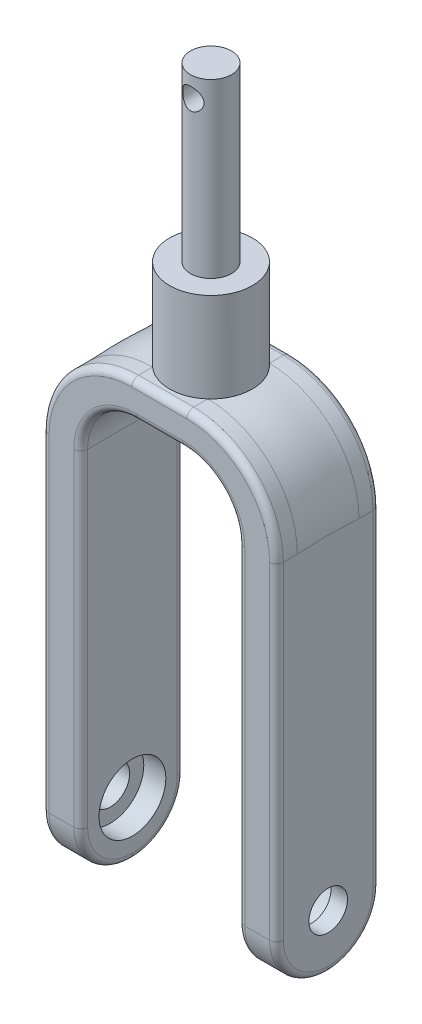
SolidWorks part; units mm, degrees
ref_plane "前视基准面" through (0, 0, 0) normal (0, 0, 1) x (1, 0, 0)
ref_plane "上视基准面" through (0, 0, 0) normal (0, 1, 0) x (1, 0, 0)
ref_plane "右视基准面" through (0, 0, 0) normal (1, 0, 0) x (0, 0, -1)
sketch "草图1" plane through (0, 0, 0) normal (0, 1, 0) x (1, 0, 0)
  line L1 (17, 7.5) -> (-17, 7.5)
  line L2 (17, 7.5) -> (17, -7.5)
  line L3 (17, -7.5) -> (-17, -7.5)
  line L4 (-17, 7.5) -> (-17, -7.5)
  line L5 (17, 7.5) -> (-17, -7.5) construction
  line L6 (17, -7.5) -> (-17, 7.5) construction
  point P0 (0, 0)
extrude "凸台-拉伸1" add sketch "草图1" against normal blind 68
sketch "草图2" plane through (0, 0, 0) normal (0, 1, 0) x (1, 0, 0)
  circle A0 centre (0, 0) radius 6
extrude "凸台-拉伸2" add sketch "草图2" along normal blind 13
sketch "草图7" plane through (0, 13, 0) normal (0, 1, 0) x (1, 0, 0)
  circle A0 centre (0, 0) radius 2.98
extrude "凸台-拉伸3" add sketch "草图7" along normal blind 25
sketch "草图8" plane through (0, 0, 0) normal (0, 0, 1) x (1, 0, 0)
  line L0 (0, 13) -> (0, 35) construction
  line L1 (6, 13) -> (-6, 13) construction
  circle A1 centre (0, 35) radius 1.55
extrude "切除-拉伸5" cut sketch "草图8" against normal through all both and the other way through all
sketch "草图3" plane through (0, 0, 7.5) normal (0, 0, 1) x (1, 0, 0)
  line L0 (-17, -68) -> (17, -68) construction
  line L1 (-11.4, -68) -> (11.4, -68)
  line L2 (-11.4, -68) -> (-11.4, -5)
  line L3 (-11.4, -5) -> (11.4, -5)
  line L4 (11.4, -68) -> (11.4, -5)
extrude "切除-拉伸1" cut sketch "草图3" against normal through all
fillet "圆角1" radius 8 2 edges at (11.4, -5, 0) (-11.4, -5, 0)
fillet "圆角5" radius 13 2 edges at (17, 0, 0) (-17, 0, 0)
fillet "圆角3" radius 7.5 4 edges at (14.2, -68, -7.5) (14.2, -68, 7.5) (-14.2, -68, -7.5) (-14.2, -68, 7.5)
fillet "圆角2" radius 1 28 edges at (-17, -36.75, -7.5) (0, 0, -7.5) (17, -36.75, -7.5) (17, -36.75, 7.5) (0, 0, 7.5) (-17, -36.75, 7.5) (-9.0569, -7.3431, 7.5) (0, -5, 7.5) (9.0569, -7.3431, 7.5) (11.4, -36.75, 7.5) (11.4, -36.75, -7.5) (9.0569, -7.3431, -7.5) (0, -5, -7.5) (-9.0569, -7.3431, -7.5) (-11.4, -36.75, -7.5) (-11.4, -36.75, 7.5) (11.4, -65.8033, 5.3033) (11.4, -65.8033, -5.3033) (-11.4, -65.8033, -5.3033) (-11.4, -65.8033, 5.3033) (-17, -65.8033, 5.3033) (-17, -65.8033, -5.3033) (17, -65.8033, -5.3033) (17, -65.8033, 5.3033) (-13.1924, -3.8076, -7.5) (13.1924, -3.8076, -7.5) (13.1924, -3.8076, 7.5) (-13.1924, -3.8076, 7.5)
sketch "草图4" plane through (17, 0, 0) normal (1, 0, 0) x (0, 0, -1)
  circle A0 centre (0, -60) radius 2.8
extrude "切除-拉伸2" cut sketch "草图4" against normal through all
sketch "草图6" plane through (11.4, 0, 0) normal (1, 0, 0) x (0, 0, -1)
  circle A0 centre (0, -60) radius 4.85
extrude "切除-拉伸4" cut sketch "草图6" along normal blind 3.2
mirror "镜向1" about plane through (0, 0, 0) normal (1, 0, 0) of "切除-拉伸4"
